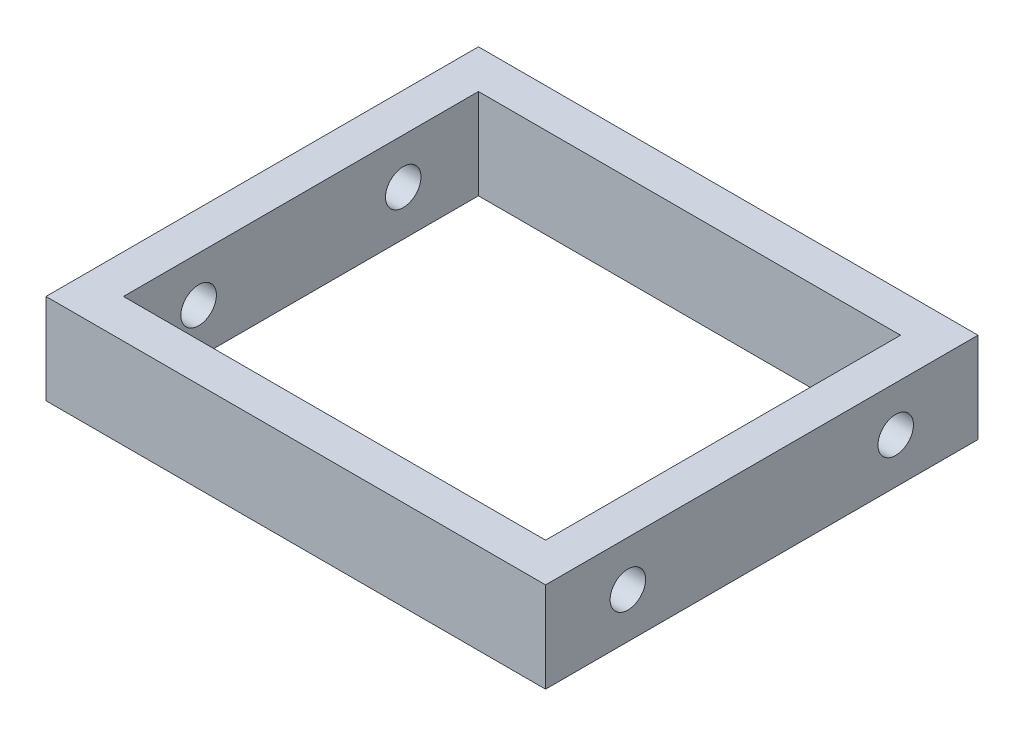
SolidWorks part; units mm, degrees
ref_plane "Front Plane" through (0, 0, 0) normal (0, 0, 1) x (1, 0, 0)
ref_plane "Top Plane" through (0, 0, 0) normal (0, 1, 0) x (1, 0, 0)
ref_plane "Right Plane" through (0, 0, 0) normal (1, 0, 0) x (0, 0, -1)
sketch "Sketch1" plane through (0, 0, 0) normal (0, 1, 0) x (1, 0, 0)
  line L1 (-32.7, -27.5) -> (32.7, -27.5)
  line L2 (-32.7, -27.5) -> (-32.7, 27.5)
  line L3 (-32.7, 27.5) -> (32.7, 27.5)
  line L4 (32.7, -27.5) -> (32.7, 27.5)
  line L5 (-32.7, -27.5) -> (32.7, 27.5) construction
  line L6 (-32.7, 27.5) -> (32.7, -27.5) construction
  line L7 (-38.7, -33.5) -> (38.7, -33.5)
  line L8 (-38.7, -33.5) -> (-38.7, 33.5)
  line L9 (-38.7, 33.5) -> (38.7, 33.5)
  line L10 (38.7, -33.5) -> (38.7, 33.5)
  line L11 (-38.7, -33.5) -> (38.7, 33.5) construction
  line L12 (-38.7, 33.5) -> (38.7, -33.5) construction
  circle A0 centre (-12.4, 0) radius 4
  circle A1 centre (53.6, 0) radius 4
  point P0 (0, 0)
  point P6 (0, 0)
  point P15 (-38.7, 41.2096)
  point P16 (0, 0)
  point P17 (0, 0)
  point P18 (-38.7, 28.0925)
  dimension "D3" = 8
  dimension "D1" = 20.3
  dimension "D2" = 14.9
  dimension "D4" = 66
  dimension "D5" = 6
  dimension "D6" = 6
  dimension "D7" = 55
extrude "Boss-Extrude1" add sketch "Sketch1" along normal blind 14 contours L7 L10 L9 L8 L4 L1 L2 L3 region at (-37.6763, 0, 0)
sketch "Sketch2" plane through (38.7, 0, 0) normal (1, 0, 0) x (0, 0, -1)
  line L0 (-20.75, 7) -> (20.75, 7) construction
  line L1 (33.5, 14) -> (33.5, 0) construction
  circle A0 centre (-20.75, 7) radius 2.75
  circle A1 centre (20.75, 7) radius 2.75
  point P4 (33.5, 7)
  point P5 (0, 7)
  dimension "D1" = 5.5
  dimension "D2" = 41.5
extrude "Cut-Extrude1" cut sketch "Sketch2" against normal up to surface (6 mm away) up to face at (32.7, 7, 0)
sketch "Sketch3" plane through (-32.7, 0, 0) normal (1, 0, 0) x (0, 0, -1)
  line L0 (15.85, 7) -> (-15.85, 7) construction
  line L3 (-15.85, 7) -> (-33.5, 7) construction
  line L4 (-33.5, 14) -> (-33.5, 0) construction
  circle A0 centre (15.85, 7) radius 2.75
  circle A1 centre (-15.85, 7) radius 2.75
  point P0 (0, 7)
  dimension "D2" = 5.5
  dimension "D1" = 31.7
extrude "Cut-Extrude2" cut sketch "Sketch3" against normal up to surface (6 mm away) up to face at (-38.7, 7, 0)
